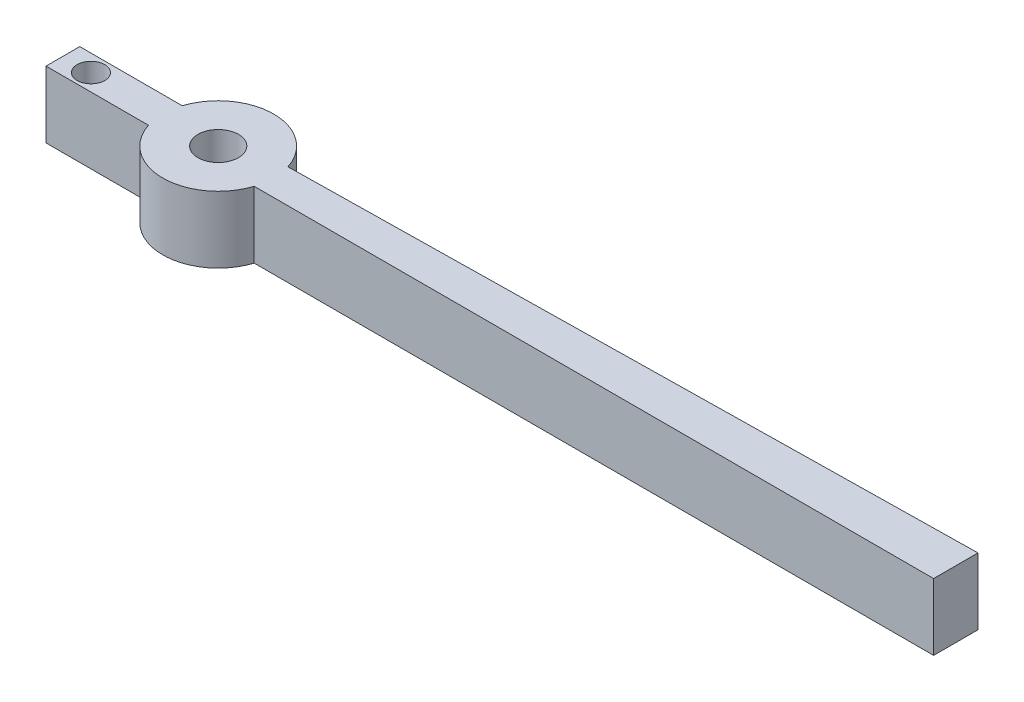
SolidWorks part; units mm, degrees
ref_plane "Front Plane" through (0, 0, 0) normal (0, 0, 1) x (1, 0, 0)
ref_plane "Top Plane" through (0, 0, 0) normal (0, 1, 0) x (1, 0, 0)
ref_plane "Right Plane" through (0, 0, 0) normal (1, 0, 0) x (0, 0, -1)
sketch "Sketch1" plane through (0, 0, 0) normal (0, 1, 0) x (1, 0, 0)
  line L1 (-194.4849, -50.3046) -> (-148.2987, -50.3046)
  line L2 (-194.4849, -50.3046) -> (-194.4849, -65.5235)
  line L3 (-194.4849, -65.5235) -> (-148.2987, -65.5235)
  line L4 (205.5151, -45.5235) -> (205.5151, -65.5235)
  line L6 (-100.6711, -65.5235) -> (205.5151, -65.5235)
  line L7 (-100.6711, -50.3046) -> (205.5151, -45.5235)
  arc A0 (-100.6711, -50.3046) -> (-148.2987, -50.3046) centre (-124.4849, -57.914) ccw
  circle A1 centre (-124.4849, -57.914) radius 9.1261
  arc A2 (-148.2987, -65.5235) -> (-100.6711, -65.5235) centre (-124.4849, -57.914) ccw
  circle A3 centre (-181.8266, -57.914) radius 6.2325
  dimension "D4" = 18.2522
  dimension "D5" = 25
  dimension "D1" = 400
  dimension "D2" = 20
  dimension "D3" = 70
  dimension "D6" = 15.2189
  dimension "D7" = 0.895
extrude "Boss-Extrude1" add sketch "Sketch1" along normal blind 15 and the other way blind 15
